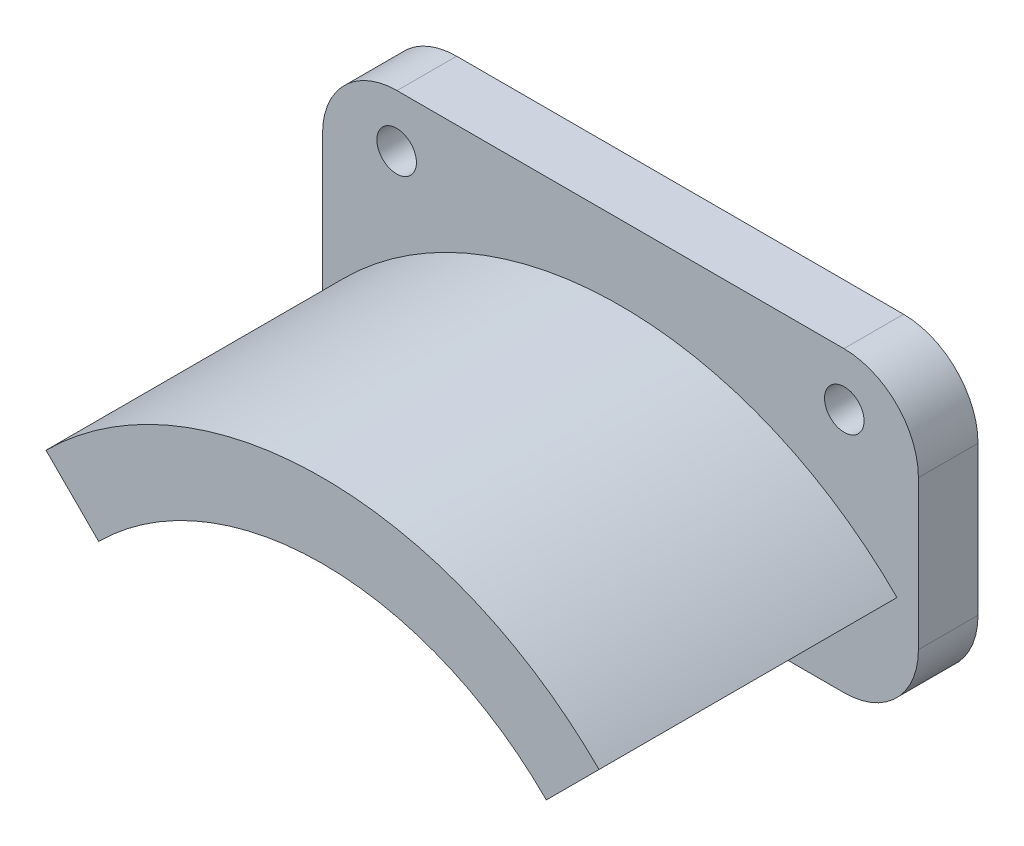
SolidWorks part; units mm, degrees
ref_plane "Front Plane" through (0, 0, 0) normal (0, 0, 1) x (1, 0, 0)
ref_plane "Top Plane" through (0, 0, 0) normal (0, 1, 0) x (1, 0, 0)
ref_plane "Right Plane" through (0, 0, 0) normal (1, 0, 0) x (0, 0, -1)
sketch "Sketch1" plane through (0, 0, 0) normal (0, 0, 1) x (1, 0, 0)
  line L0 (18.5616, -2.6884) -> (15.026, -6.224)
  line L1 (-20, 10) -> (20, 10)
  line L2 (-20, 10) -> (-20, -10)
  line L3 (-20, -10) -> (20, -10)
  line L4 (20, 10) -> (20, -10)
  line L5 (-20, 10) -> (20, -10) construction
  line L6 (-20, -10) -> (20, 10) construction
  line L7 (0, -21.25) -> (0, 10) construction
  line L8 (-18.5616, -2.6884) -> (-15.026, -6.224)
  circle A0 centre (0, -21.25) radius 21.25
  circle A1 centre (0, -21.25) radius 26.25
  point P0 (0, 0)
  dimension "D2" = 42.5
  dimension "D3" = 52.5
  dimension "D1" = 45
  dimension "D4" = 20
  dimension "D5" = 40
extrude "Boss-Extrude1" add sketch "Sketch1" along normal blind 20 contours L0 A1 L8 A0 region at (0, 0.2115, 0)
extrude "Boss-Extrude2" add sketch "Sketch1<3>" against normal blind 4 separate body contours A1 L4 L1 L2 | L3 A0 | L4 A1 L0 A0 L3 | L8 A1 L2 L3 A0 region at (18.1597, -6.5433, 0) region at (0, 5.6348, 0) region at (0, -5.9065, 0) region at (-18.1597, -6.5433, 0)
sketch "Sketch1<3>" plane through (0, 0, 0) normal (0, 0, 1) x (1, 0, 0) same geometry as "Sketch1"
fillet "Fillet1" radius 5 4 edges at (20, 10, -2) (20, -10, -2) (-20, -10, -2) (-20, 10, -2)
sketch "Sketch2" plane through (0, 0, 0) normal (0, 0, 1) x (1, 0, 0)
  line L0 (0, 10) -> (0, -10) construction
  line L1 (-15, 10) -> (15, 10) construction
  line L2 (-15, -10) -> (15, -10) construction
  circle A0 centre (0.0246, -21.0311) radius 26.0298 construction
  circle A1 centre (0.0246, -21.0311) radius 21.0298 construction
  circle A2 centre (0.0246, -21.0311) radius 20 construction
  circle A3 centre (0.0246, -21.0311) radius 27.5 construction
  circle A4 centre (15.0246, 6.4689) radius 1.3272
  circle A5 centre (0, -6.0311) radius 1.25
  circle A6 centre (-15.0246, 6.4689) radius 1.3272
  dimension "D1" = 40
  dimension "D2" = 55
  dimension "D4" = 2.5
  dimension "D5" = 15
  dimension "D3" = 15
  dimension "D6" = 27.5
extrude "Cut-Extrude1" cut sketch "Sketch2" against normal through all both and the other way through all
equation "\"constraint_angle_half\"= 45deg"
equation "\"theoretical_constraint_ID\"= 4cm"
equation "\"print_tolerance\"= 0.25cm"
equation "\"constraint_ID\"= \"print_tolerance\" + \"theoretical_constraint_ID\""
equation "\"theoretical_constraint_OD\"= 5.5cm"
equation "\"constraint_OD\"= \"theoretical_constraint_OD\" - \"print_tolerance\""
equation "\"plate_width\"= 2cm"
equation "\"plate_length\"= 4cm"
equation "\"plate_depth\"= 0.4cm"
equation "\"M3_ID\"= 0.25cm"
